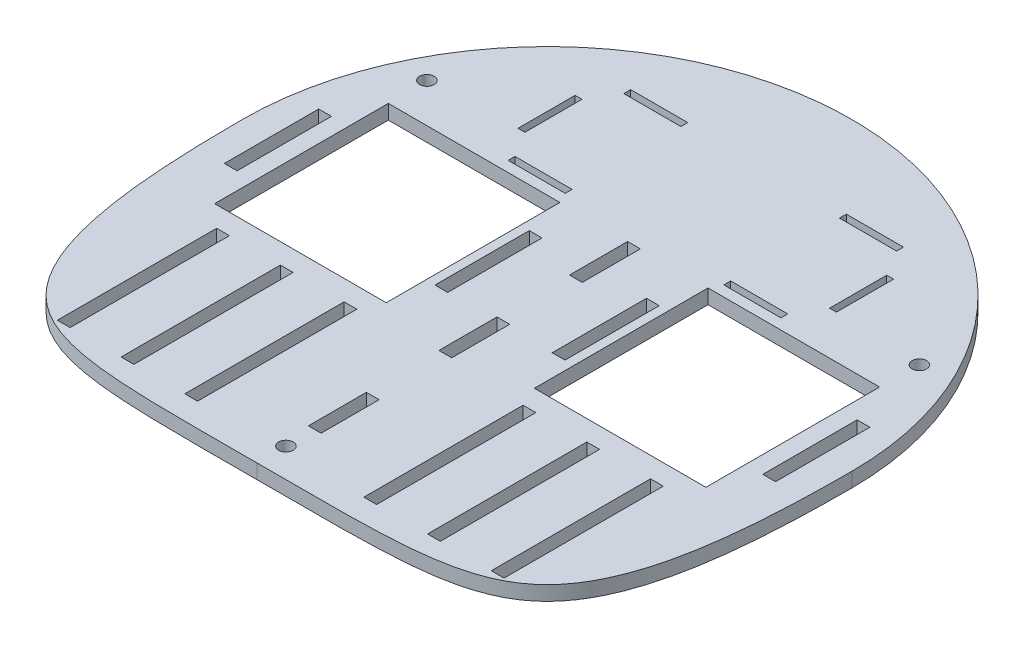
SolidWorks part; units mm, degrees
ref_plane "Front Plane" through (0, 0, 0) normal (0, 0, 1) x (1, 0, 0)
ref_plane "Top Plane" through (0, 0, 0) normal (0, 1, 0) x (1, 0, 0)
ref_plane "Right Plane" through (0, 0, 0) normal (1, 0, 0) x (0, 0, -1)
sketch "Sketch1" plane through (0, 0, 0) normal (0, 1, 0) x (1, 0, 0)
  line L0 (0, 0) -> (-157.9039, -157.9039) construction
  line L1 (0, -127) -> (0, 133.35) construction
  arc A0 (133.35, 0) -> (-133.35, 0) centre (0, 0) ccw
  spline S0 degree 3 poles (-133.35, 0) (-133.35, -51.198) (-123.8034, -129.8051) (-58.428, -127) (0, -127) knots 0 0 0 0 0.502616 1 1 1 1
  spline S1 degree 3 poles (133.35, 0) (133.35, -51.198) (123.8034, -129.8051) (58.428, -127) (0, -127) knots 0 0 0 0 0.502616 1 1 1 1
  dimension "D1" = 266.7
extrude "Base" add sketch "Sketch1" along normal blind 6.35
sketch "ShaftLayout" plane through (0, 6.35, 0) normal (0, 1, 0) x (1, 0, 0)
  line L0 (-133.35, 0) -> (133.35, 0) construction
  line L1 (0, 133.35) -> (0, -127) construction
  line L2 (-113.4353, -6.35) -> (-103.5293, -6.35)
  line L3 (-36.3853, -38) -> (-94.3853, -38)
  line L4 (-36.3853, -38) -> (-36.3853, 38)
  line L5 (-36.3853, 38) -> (-94.3853, 38)
  line L6 (-94.3853, -38) -> (-94.3853, 38)
  line L7 (-36.3853, -38) -> (-94.3853, 38) construction
  line L8 (-36.3853, 38) -> (-94.3853, -38) construction
  line L9 (-100.7353, -15.875) -> (-103.5293, -15.875)
  line L10 (-100.7353, -15.875) -> (-100.7353, 15.875)
  line L11 (-100.7353, 15.875) -> (-103.5293, 15.875)
  line L12 (-103.5293, -15.875) -> (-103.5293, 15.875)
  line L13 (-100.7353, -15.875) -> (-103.5293, 15.875) construction
  line L14 (-100.7353, 15.875) -> (-103.5293, -15.875) construction
  line L15 (-113.4353, -6.35) -> (-113.4353, 6.35)
  line L16 (-103.5293, -6.35) -> (-103.5293, 6.35)
  line L17 (-113.4353, 6.35) -> (-103.5293, 6.35)
  line L18 (-113.4353, -6.35) -> (-103.5293, 6.35) construction
  line L19 (-103.5293, -6.35) -> (-113.4353, 6.35) construction
  line L20 (-115.0228, -9.525) -> (-113.4353, -9.525)
  line L21 (-115.0228, -9.525) -> (-115.0228, 9.525)
  line L22 (-113.4353, -9.525) -> (-113.4353, 9.525)
  line L23 (-115.0228, 9.525) -> (-113.4353, 9.525)
  line L24 (-115.0228, -9.525) -> (-113.4353, 9.525) construction
  line L25 (-113.4353, -9.525) -> (-115.0228, 9.525) construction
  line L26 (-126.1353, -7.9375) -> (-115.0228, -7.9375)
  line L27 (-126.1353, -7.9375) -> (-126.1353, 7.9375)
  line L28 (-115.0228, -7.9375) -> (-115.0228, 7.9375)
  line L29 (-126.1353, 7.9375) -> (-115.0228, 7.9375)
  line L30 (-126.1353, -7.9375) -> (-115.0228, 7.9375) construction
  line L31 (-115.0228, -7.9375) -> (-126.1353, 7.9375) construction
  line L32 (-17.3353, -7.9375) -> (-28.4478, -7.9375)
  line L33 (-30.0353, -9.525) -> (-28.4478, -9.525)
  line L34 (-30.0353, -9.525) -> (-30.0353, 9.525)
  line L35 (-30.0353, 9.525) -> (-28.4478, 9.525)
  line L36 (-28.4478, -9.525) -> (-28.4478, 9.525)
  line L37 (-30.0353, -9.525) -> (-28.4478, 9.525) construction
  line L38 (-30.0353, 9.525) -> (-28.4478, -9.525) construction
  line L39 (-17.3353, -7.9375) -> (-17.3353, 7.9375)
  line L40 (-28.4478, -7.9375) -> (-28.4478, 7.9375)
  line L41 (-17.3353, 7.9375) -> (-28.4478, 7.9375)
  line L42 (-17.3353, -7.9375) -> (-28.4478, 7.9375) construction
  line L43 (-28.4478, -7.9375) -> (-17.3353, 7.9375) construction
  arc A0 (133.35, 0) -> (-133.35, 0) centre (0, 0) ccw construction
  point P10 (-65.3853, 0)
  point P15 (-102.1323, 0)
  point P20 (-29.2416, 0)
  point P21 (-108.4823, 0)
  point P22 (-114.2291, 0)
  point P23 (-120.5791, 0)
  point P41 (-22.8916, 0)
  dimension "D1" = 58
  dimension "D2" = 76
  dimension "D3" = 6.35
  dimension "D4" = 2.794
  dimension "D5" = 31.75
  dimension "D6" = 9.906
  dimension "D7" = 12.7
  dimension "D8" = 19.05
  dimension "D9" = 1.5875
  dimension "D10" = 12.7
  dimension "D11" = 15.875
  dimension "D12" = 19.05
  dimension "D13" = 1.5875
  dimension "D14" = 15.875
  dimension "D15" = 12.7
  dimension "D16" = 6.35
sketch "MotorLayout" plane through (0, 6.35, 0) normal (0, 1, 0) x (1, 0, 0)
  line L0 (-97.7353, -81.74) -> (-117.7353, -81.74) construction
  line L1 (-97.7353, -110.24) -> (-21.7353, -110.24)
  line L2 (-97.7353, -110.24) -> (-97.7353, -53.24)
  line L3 (-97.7353, -53.24) -> (-21.7353, -53.24)
  line L4 (-21.7353, -110.24) -> (-21.7353, -53.24)
  line L5 (-97.7353, -110.24) -> (-21.7353, -53.24) construction
  line L6 (-97.7353, -53.24) -> (-21.7353, -110.24) construction
  line L7 (-113.4353, -92.0587) -> (-103.5293, -92.0587)
  line L8 (-103.5293, -97.615) -> (-100.7353, -97.615)
  line L9 (-103.5293, -97.615) -> (-103.5293, -65.865)
  line L10 (-103.5293, -65.865) -> (-100.7353, -65.865)
  line L11 (-100.7353, -97.615) -> (-100.7353, -65.865)
  line L12 (-103.5293, -97.615) -> (-100.7353, -65.865) construction
  line L13 (-103.5293, -65.865) -> (-100.7353, -97.615) construction
  line L14 (-36.3853, -38) -> (-94.3853, -38) construction
  line L15 (-113.4353, -92.0587) -> (-113.4353, -71.4212)
  line L16 (-103.5293, -92.0587) -> (-103.5293, -71.4212)
  line L17 (-113.4353, -71.4212) -> (-103.5293, -71.4212)
  line L18 (-113.4353, -92.0587) -> (-103.5293, -71.4212) construction
  line L19 (-103.5293, -92.0587) -> (-113.4353, -71.4212) construction
  line L20 (-102.1323, -1000) -> (-102.1323, 49000) construction
  point P0 (-59.7353, -81.74)
  point P7 (-102.1323, -81.74)
  point P14 (-108.4823, -81.74)
  dimension "D1" = 20
  dimension "D2" = 76
  dimension "D3" = 57
  dimension "D4" = 2.794
  dimension "D5" = 15.24
  dimension "D6" = 31.75
  dimension "D7" = 20.6375
  dimension "D8" = 12.7
  dimension "D9" = 3
sketch "Sketch6" plane through (0, 6.35, 0) normal (0, 1, 0) x (1, 0, 0)
  line L0 (-36.3853, -38) -> (-36.3853, 38) construction
  line L1 (-32.4166, -38) -> (-107.4981, -38)
  line L2 (-32.4166, -38) -> (-32.4166, 38)
  line L3 (-32.4166, 38) -> (-107.4981, 38)
  line L4 (-107.4981, -38) -> (-107.4981, 38)
  line L5 (-28.4478, -9.525) -> (-28.4478, 9.525) construction
  line L6 (-103.5293, -15.875) -> (-103.5293, 15.875) construction
  line L7 (0, 133.35) -> (0, -127) construction
  line L8 (28.4478, 20.6375) -> (22.8598, -20.6375) construction
  line L9 (28.4478, -20.6375) -> (22.8598, 20.6375) construction
  line L10 (115.0228, 20.6375) -> (120.6108, -20.6375) construction
  line L11 (115.0228, -20.6375) -> (120.6108, 20.6375) construction
  line L12 (-133.35, 0) -> (133.35, 0) construction
  line L13 (-115.0228, -20.6375) -> (-120.6108, -20.6375)
  line L14 (-115.0228, -20.6375) -> (-115.0228, 20.6375)
  line L15 (-115.0228, 20.6375) -> (-120.6108, 20.6375)
  line L16 (-120.6108, -20.6375) -> (-120.6108, 20.6375)
  line L17 (-115.0228, -20.6375) -> (-120.6108, 20.6375) construction
  line L18 (-115.0228, 20.6375) -> (-120.6108, -20.6375) construction
  line L19 (-115.0228, -9.525) -> (-115.0228, 9.525) construction
  line L20 (-126.1353, 7.9375) -> (-115.0228, 7.9375) construction
  line L21 (-17.3353, 7.9375) -> (-28.4478, 7.9375) construction
  line L22 (-28.4478, -20.6375) -> (-22.8598, -20.6375)
  line L23 (-28.4478, -20.6375) -> (-28.4478, 20.6375)
  line L24 (-28.4478, 20.6375) -> (-22.8598, 20.6375)
  line L25 (-22.8598, -20.6375) -> (-22.8598, 20.6375)
  line L26 (-28.4478, -20.6375) -> (-22.8598, 20.6375) construction
  line L27 (-28.4478, 20.6375) -> (-22.8598, -20.6375) construction
  line L28 (22.8598, -20.6375) -> (22.8598, 20.6375)
  line L29 (28.4478, 20.6375) -> (22.8598, 20.6375)
  line L30 (28.4478, -20.6375) -> (28.4478, 20.6375)
  line L31 (28.4478, -20.6375) -> (22.8598, -20.6375)
  line L32 (120.6108, -20.6375) -> (120.6108, 20.6375)
  line L33 (115.0228, 20.6375) -> (120.6108, 20.6375)
  line L34 (115.0228, -20.6375) -> (115.0228, 20.6375)
  line L35 (115.0228, -20.6375) -> (120.6108, -20.6375)
  line L36 (107.4981, -38) -> (107.4981, 38)
  line L37 (32.4166, 38) -> (107.4981, 38)
  line L38 (32.4166, -38) -> (32.4166, 38)
  line L39 (32.4166, -38) -> (107.4981, -38)
  point P16 (-117.8168, 0)
  point P27 (-25.6538, 0)
  point P44 (25.6538, 0)
  point P45 (117.8168, 0)
  dimension "D1" = 3.9688
  dimension "D2" = 3.9688
  dimension "D3" = 12.7
  dimension "D4" = 12.7
  dimension "D5" = 5.588
  dimension "D6" = 5.588
extrude "WheelShaftCut" cut sketch "Sketch6" against normal through all
sketch "Sketch8" plane through (0, 6.35, 0) normal (0, 1, 0) x (1, 0, 0)
  line L0 (-97.7353, -81.74) -> (-21.7353, -81.74) construction
  line L1 (-21.7353, -110.24) -> (-21.7353, -53.24) construction
  line L2 (-97.7353, -53.24) -> (-21.7353, -53.24) construction
  line L3 (-36.3805, -116.59) -> (-41.9685, -116.59)
  line L4 (-36.3805, -116.59) -> (-36.3805, -46.89)
  line L5 (-36.3805, -46.89) -> (-41.9685, -46.89)
  line L6 (-41.9685, -116.59) -> (-41.9685, -46.89)
  line L7 (-36.3805, -116.59) -> (-41.9685, -46.89) construction
  line L8 (-36.3805, -46.89) -> (-41.9685, -116.59) construction
  line L9 (-64.2639, -116.59) -> (-69.8519, -116.59)
  line L10 (-64.2639, -116.59) -> (-64.2639, -46.89)
  line L11 (-64.2639, -46.89) -> (-69.8519, -46.89)
  line L12 (-69.8519, -116.59) -> (-69.8519, -46.89)
  line L13 (-64.2639, -116.59) -> (-69.8519, -46.89) construction
  line L14 (-64.2639, -46.89) -> (-69.8519, -116.59) construction
  line L15 (-92.1473, -116.59) -> (-97.7353, -116.59)
  line L16 (-92.1473, -116.59) -> (-92.1473, -46.89)
  line L17 (-92.1473, -46.89) -> (-97.7353, -46.89)
  line L18 (-97.7353, -116.59) -> (-97.7353, -46.89)
  line L19 (-92.1473, -116.59) -> (-97.7353, -46.89) construction
  line L20 (-92.1473, -46.89) -> (-97.7353, -116.59) construction
  line L21 (-97.7353, -110.24) -> (-97.7353, -53.24) construction
  line L22 (0, 133.35) -> (0, -127) construction
  line L23 (92.1473, -46.89) -> (97.7353, -116.59) construction
  line L24 (92.1473, -116.59) -> (97.7353, -46.89) construction
  line L25 (64.2639, -46.89) -> (69.8519, -116.59) construction
  line L26 (64.2639, -116.59) -> (69.8519, -46.89) construction
  line L27 (36.3805, -46.89) -> (41.9685, -116.59) construction
  line L28 (36.3805, -116.59) -> (41.9685, -46.89) construction
  line L29 (97.7353, -81.74) -> (21.7353, -81.74) construction
  line L30 (97.7353, -116.59) -> (97.7353, -46.89)
  line L31 (92.1473, -46.89) -> (97.7353, -46.89)
  line L32 (92.1473, -116.59) -> (92.1473, -46.89)
  line L33 (92.1473, -116.59) -> (97.7353, -116.59)
  line L34 (69.8519, -116.59) -> (69.8519, -46.89)
  line L35 (64.2639, -46.89) -> (69.8519, -46.89)
  line L36 (64.2639, -116.59) -> (64.2639, -46.89)
  line L37 (64.2639, -116.59) -> (69.8519, -116.59)
  line L38 (41.9685, -116.59) -> (41.9685, -46.89)
  line L39 (36.3805, -46.89) -> (41.9685, -46.89)
  line L40 (36.3805, -116.59) -> (36.3805, -46.89)
  line L41 (36.3805, -116.59) -> (41.9685, -116.59)
  point P5 (-39.1745, -81.74)
  point P14 (-67.0579, -81.74)
  point P19 (-94.9413, -81.74)
  point P42 (94.9413, -81.74)
  point P43 (67.0579, -81.74)
  point P44 (39.1745, -81.74)
  dimension "D1" = 5.588
  dimension "D2" = 6.35
  dimension "D3" = 3
extrude "MotorCut" cut sketch "Sketch8" against normal through all
sketch "BatteryLayout" plane through (0, 6.35, 0) normal (0, 1, 0) x (1, 0, 0)
  line L0 (0, 133.35) -> (0, -127) construction
  line L1 (-32.4166, 38) -> (-107.4981, 38) construction
  line L2 (-66.675, 45.62) -> (66.675, 45.62)
  line L3 (-66.675, 45.62) -> (-66.675, 93.245)
  line L4 (-66.675, 93.245) -> (66.675, 93.245)
  line L5 (66.675, 45.62) -> (66.675, 93.245)
  line L6 (-66.675, 45.62) -> (66.675, 93.245) construction
  line L7 (-66.675, 93.245) -> (66.675, 45.62) construction
  arc A0 (133.35, 0) -> (-133.35, 0) centre (0, 0) ccw construction
  point P6 (0, 69.4325)
  dimension "D1" = 133.35
  dimension "D2" = 47.625
  dimension "D3" = 7.62
sketch "Sketch10" plane through (0, 6.35, 0) normal (0, 1, 0) x (1, 0, 0)
  line L0 (-66.675, 93.245) -> (66.675, 93.245) construction
  line L1 (-59.69, 42.62) -> (-34.69, 42.62)
  line L2 (-59.69, 42.62) -> (-59.69, 45.62)
  line L3 (-59.69, 45.62) -> (-34.69, 45.62)
  line L4 (-34.69, 42.62) -> (-34.69, 45.62)
  line L5 (-59.69, 42.62) -> (-34.69, 45.62) construction
  line L6 (-59.69, 45.62) -> (-34.69, 42.62) construction
  line L7 (-59.69, 96.245) -> (-34.69, 96.245)
  line L8 (-59.69, 96.245) -> (-59.69, 93.245)
  line L9 (-59.69, 93.245) -> (-34.69, 93.245)
  line L10 (-34.69, 96.245) -> (-34.69, 93.245)
  line L11 (-59.69, 96.245) -> (-34.69, 93.245) construction
  line L12 (-59.69, 93.245) -> (-34.69, 96.245) construction
  line L13 (-66.675, 45.62) -> (66.675, 45.62) construction
  line L14 (-66.675, 45.62) -> (-66.675, 93.245) construction
  line L15 (0, 69.4325) -> (-66.675, 69.4325) construction
  line L16 (-66.675, 56.9325) -> (-69.675, 56.9325)
  line L17 (-66.675, 56.9325) -> (-66.675, 81.9325)
  line L18 (-66.675, 81.9325) -> (-69.675, 81.9325)
  line L19 (-69.675, 56.9325) -> (-69.675, 81.9325)
  line L20 (0, 133.35) -> (0, -127) construction
  line L21 (59.69, 93.245) -> (34.69, 96.245) construction
  line L22 (59.69, 96.245) -> (34.69, 93.245) construction
  line L23 (59.69, 45.62) -> (34.69, 42.62) construction
  line L24 (59.69, 42.62) -> (34.69, 45.62) construction
  line L25 (69.675, 56.9325) -> (69.675, 81.9325)
  line L26 (66.675, 81.9325) -> (69.675, 81.9325)
  line L27 (66.675, 56.9325) -> (66.675, 81.9325)
  line L28 (66.675, 56.9325) -> (69.675, 56.9325)
  line L29 (34.69, 96.245) -> (34.69, 93.245)
  line L30 (59.69, 93.245) -> (34.69, 93.245)
  line L31 (59.69, 96.245) -> (59.69, 93.245)
  line L32 (59.69, 96.245) -> (34.69, 96.245)
  line L33 (34.69, 42.62) -> (34.69, 45.62)
  line L34 (59.69, 45.62) -> (34.69, 45.62)
  line L35 (59.69, 42.62) -> (59.69, 45.62)
  line L36 (59.69, 42.62) -> (34.69, 42.62)
  point P0 (-47.19, 44.12)
  point P5 (-47.19, 94.745)
  point P20 (-66.675, 69.4325)
  point P40 (66.675, 69.4325)
  point P41 (47.19, 94.745)
  point P42 (47.19, 44.12)
  dimension "D1" = 3
  dimension "D2" = 3
  dimension "D3" = 25
  dimension "D4" = 25
  dimension "D5" = 6.985
  dimension "D6" = 6.985
  dimension "D7" = 3
  dimension "D8" = 25
extrude "VelcroCut" cut sketch "Sketch10" against normal through all
sketch "Sketch11" plane through (0, 6.35, 0) normal (0, 1, 0) x (1, 0, 0)
  line L0 (0, 133.35) -> (0, -127) construction
  line L1 (-133.35, 0) -> (133.35, 0) construction
  line L3 (-34.69, 45.62) -> (-59.69, 45.62) construction
  line L4 (-69.675, 81.9325) -> (-69.675, 56.9325) construction
  arc A0 (133.35, 0) -> (-133.35, 0) centre (0, 0) ccw construction
  circle A1 centre (0, -114.3) radius 3.175
  circle A2 centre (-107.775, 55.145) radius 3.175
  circle A3 centre (107.775, 55.145) radius 3.175
  dimension "D1" = 6.35
  dimension "D2" = 12.7
  dimension "D3" = 6.35
  dimension "D4" = 9.525
  dimension "D5" = 38.1
extrude "ScrewCut" cut sketch "Sketch11" against normal through all
sketch "Sketch13" plane through (0, 6.35, 0) normal (0, 1, 0) x (1, 0, 0)
  line L0 (0, 133.35) -> (0, -127) construction
  line L1 (-2.794, 12.6) -> (2.794, 12.6)
  line L2 (-2.794, 12.6) -> (-2.794, 38)
  line L3 (-2.794, 38) -> (2.794, 38)
  line L4 (2.794, 12.6) -> (2.794, 38)
  line L5 (-2.794, 12.6) -> (2.794, 38) construction
  line L6 (-2.794, 38) -> (2.794, 12.6) construction
  line L7 (107.4981, 38) -> (32.4166, 38) construction
  line L8 (-2.794, -44.55) -> (2.794, -44.55)
  line L9 (-2.794, -44.55) -> (-2.794, -19.15)
  line L10 (-2.794, -19.15) -> (2.794, -19.15)
  line L11 (2.794, -44.55) -> (2.794, -19.15)
  line L12 (-2.794, -44.55) -> (2.794, -19.15) construction
  line L13 (-2.794, -19.15) -> (2.794, -44.55) construction
  line L14 (-2.794, -101.7) -> (2.794, -101.7)
  line L15 (-2.794, -101.7) -> (-2.794, -76.3)
  line L16 (-2.794, -76.3) -> (2.794, -76.3)
  line L17 (2.794, -101.7) -> (2.794, -76.3)
  line L18 (-2.794, -101.7) -> (2.794, -76.3) construction
  line L19 (-2.794, -76.3) -> (2.794, -101.7) construction
  point P0 (0, 25.3)
  point P10 (0, -31.85)
  point P15 (0, -89)
  dimension "D1" = 5.588
  dimension "D2" = 25.4
  dimension "D3" = 0
  dimension "D4" = 3
extrude "SupportStrutCut" cut sketch "Sketch13" against normal through all
